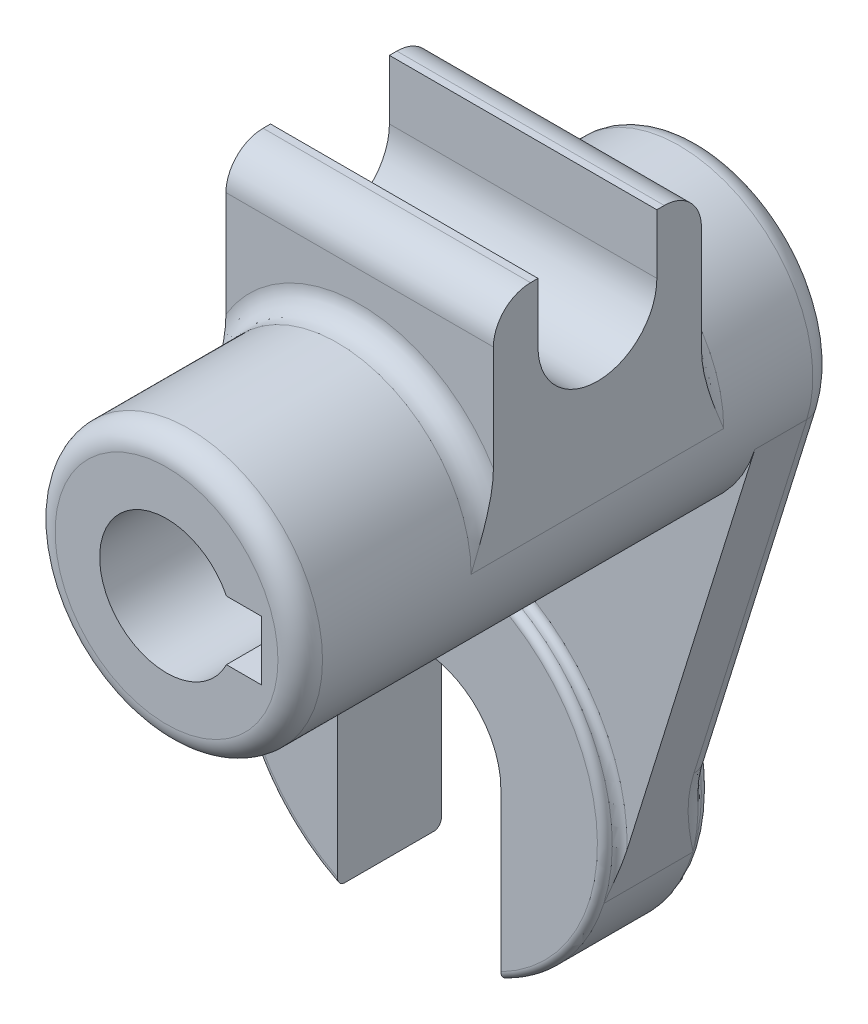
SolidWorks part; units mm, degrees
ref_plane "前视基准面" through (0, 0, 0) normal (0, 0, 1) x (1, 0, 0)
ref_plane "上视基准面" through (0, 0, 0) normal (0, 1, 0) x (1, 0, 0)
ref_plane "右视基准面" through (0, 0, 0) normal (1, 0, 0) x (0, 0, -1)
other "Configuration Table"
sketch "草图1" plane through (0, 0, 0) normal (0, 0, 1) x (1, 0, 0)
  circle A0 centre (0, 0) radius 18
  dimension "D1" = 36
extrude "凸台-拉伸1" add sketch "草图1" along normal blind 72
sketch "草图2" plane through (0, 0, 0) normal (1, 0, 0) x (0, 0, -1)
  line L0 (-88.6069, 0) -> (17.6805, 0) construction
  line L1 (-72, 18) -> (-72, -18) construction
  line L2 (-41, 30) -> (-23, 30)
  line L3 (-46, 25) -> (-46, 0)
  line L4 (-46, 0) -> (-18, 0)
  line L5 (-18, 25) -> (-18, 0)
  line L6 (-46, 30) -> (-18, 0) construction
  line L7 (-46, 0) -> (-18, 30) construction
  arc A0 (-18, 25) -> (-23, 30) centre (-23, 25) ccw
  arc A1 (-46, 25) -> (-41, 30) centre (-41, 25) cw
  point P3 (-32, 15)
  dimension "D4" = 5
  dimension "D1" = 30
  dimension "D2" = 28
  dimension "D3" = 40
extrude "凸台-拉伸2" add sketch "草图2" along normal mid plane 36
sketch "草图3" plane through (0, 0, 0) normal (1, 0, 0) x (0, 0, -1)
  line L0 (-32, 22) -> (-32, 38) construction
  line L1 (-23, 30) -> (-41, 30) construction
  line L2 (-40, 22) -> (-40, 38)
  line L3 (-24, 22) -> (-24, 38)
  arc A0 (-40, 22) -> (-24, 22) centre (-32, 22) ccw
  arc A1 (-24, 38) -> (-40, 38) centre (-32, 38) ccw
  point P4 (-32, 30)
  point P9 (0, 0)
  dimension "D1" = 8
  dimension "D2" = 22
extrude "切除-拉伸1" cut sketch "草图3" against normal through all both and the other way through all
ref_plane "基准面1" through (0, 0, 5) normal (0, 0, 1) x (1, 0, 0)
sketch "草图4" plane through (0, 0, 5) normal (0, 0, 1) x (1, 0, 0)
  line L0 (-37, -60) -> (-37, -82.4499)
  line L1 (-15, -60) -> (-15, -82.4499)
  arc A0 (-15, -82.4499) -> (-37, -82.4499) centre (-26, -60) ccw
  arc A1 (-15, -60) -> (-37, -60) centre (-26, -60) ccw
  point P7 (1.1794, -36.7975)
  point P8 (4.931, -29.5828)
  dimension "D1" = 25
  dimension "D2" = 11
  dimension "D3" = 26
  dimension "D4" = 60
extrude "凸台-拉伸3" add sketch "草图4" along normal mid plane 14 separate body
sketch "草图5" plane through (0, 0, 5) normal (0, 0, 1) x (1, 0, 0)
  line L0 (-15.655, 8.8838) -> (-47.743, -47.6614)
  line L1 (17.1872, -5.3478) -> (-2.1288, -67.4275)
  circle A5 centre (0, 0) radius 18 construction
  arc A6 (-15, -82.4499) -> (-37, -82.4499) centre (-26, -60) ccw construction
  arc A7 (-2.1288, -67.4275) -> (-47.743, -47.6614) centre (-26, -60) ccw
  arc A8 (-15.655, 8.8838) -> (17.1872, -5.3478) centre (0, 0) ccw
extrude "凸台-拉伸4" add sketch "草图5" along normal mid plane 10
sketch "草图6" plane through (0, 0, 5) normal (0, 0, 1) x (1, 0, 0)
  line L0 (0, 0) -> (-26, -60) construction
  line L1 (0, 0) -> (77.6982, -33.6692) construction
ref_plane "基准面2" through (0, 0, 0) normal (0.9176, -0.3976, 0) x (0, 0, -1)
sketch "草图7" plane through (0, 0, 0) normal (0.9176, -0.3976, 0) x (0, 0, -1)
  line L0 (-55, -18) -> (-10, -36)
  line L1 (-72, -18) -> (-10, -18) construction
  line L2 (-10, -62.7149) -> (-10, 1.9269) construction
  point P2 (0, 0)
  dimension "D1" = 45
  dimension "D2" = 18
rib "筋6" sketch "草图7" sketch "草图7" thickness 10 extrusion direction parallel to sketch draft on no parameters "D1"=10
sketch "草图8" plane through (0, 0, 0) normal (0, 0, 1) x (1, 0, 0)
  line L0 (-46.8357, 0) -> (60.2353, 0) construction
  line L2 (8.0623, 4) -> (12.8, 4)
  line L4 (8.0623, -4) -> (12.8, -4)
  line L5 (12.8, 4) -> (12.8, -4)
  arc A0 (8.0623, 4) -> (8.0623, -4) centre (0, 0) ccw
  dimension "D1" = 18
  dimension "D2" = 12.8
  dimension "D3" = 8
extrude "切除-拉伸4" cut sketch "草图8" along normal up to surface (72 mm away) up to face at (18, 0, 72)
fillet "圆角1" radius 1 4 edges at (-16.0598, -37.0611, 10) (-26, -35, -2) (-16.0598, -37.0611, 0) (-26, -35, 12)
fillet "圆角2" radius 3 8 edges at (-0.6013, -62.5182, -0.121) (8.5901, -32.9782, 0) (-45.2055, -43.1898, -0.121) (-29.9367, -16.2833, 0) (0, 18, 18) (7.1569, 16.516, 0) (0, 18, 46) (18, 0, 72)
